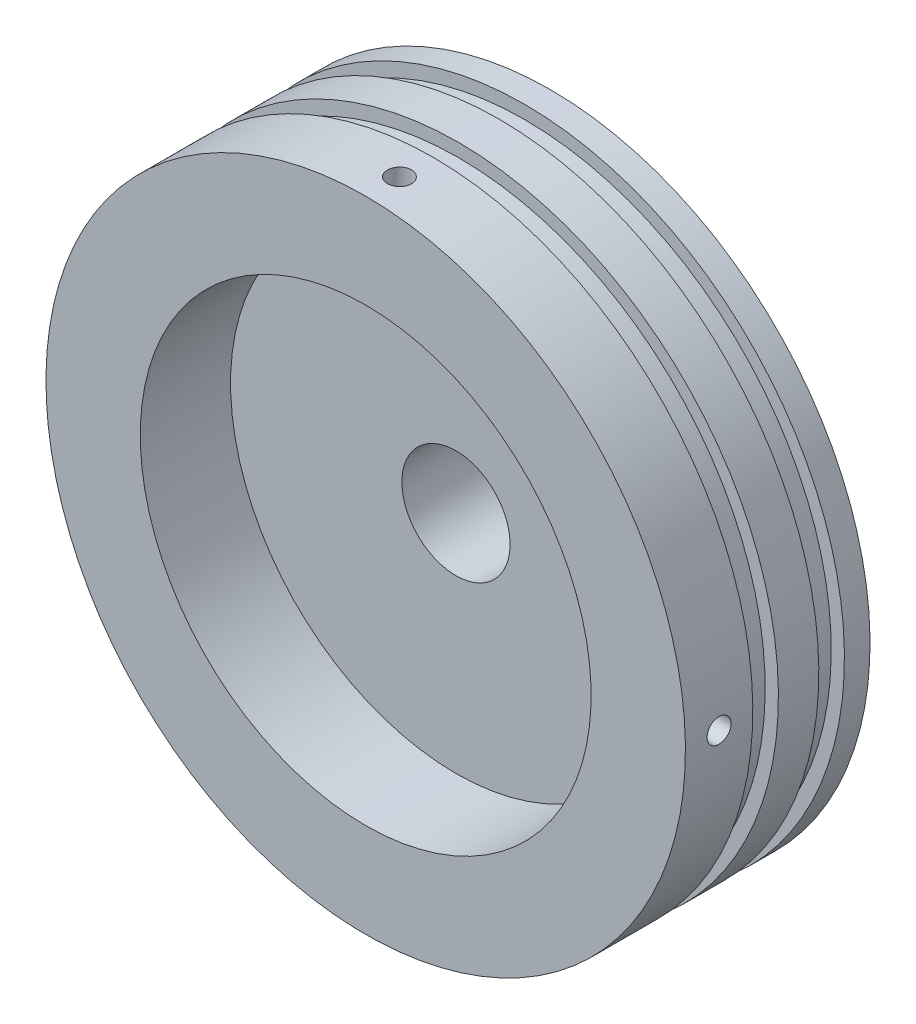
SolidWorks part; units mm, degrees
ref_plane "XY" through (0, 0, 0) normal (0, 0, 1) x (1, 0, 0)
ref_plane "XZ" through (0, 0, 0) normal (0, 1, 0) x (1, 0, 0)
ref_plane "YZ" through (0, 0, 0) normal (1, 0, 0) x (0, 0, -1)
ref_axis "X" through (-33.1508, 0, 0) along (1, 0, 0)
ref_axis "Y" through (0, -33.1508, 0) along (0, 1, 0)
ref_axis "Z" through (0, 0, 18.269) along (0, 0, -1)
sketch "Sketch2" plane through (0, 0, 0) normal (1, 0, 0) x (0, 0, -1)
  line L2 (-17.399, 30.1371) -> (-11.049, 30.1371)
  line L3 (-11.049, 30.1371) -> (-11.049, 28.8925)
  line L4 (-11.049, 28.8925) -> (-8.636, 28.8925)
  line L5 (-8.636, 28.8925) -> (-8.636, 30.1371)
  line L6 (-8.636, 30.1371) -> (-4.826, 30.1371)
  line L7 (-4.826, 30.1371) -> (-4.826, 28.8925)
  line L8 (-4.826, 28.8925) -> (-2.413, 28.8925)
  line L9 (-2.413, 28.8925) -> (-2.413, 30.1371)
  line L10 (-2.413, 30.1371) -> (0, 30.1371)
  line L11 (0, 30.1371) -> (0, 0)
  line L12 (0, 0) -> (-8.89, 0)
  line L13 (-17.399, 30.1371) -> (-17.399, 21.2471)
  line L14 (-17.399, 21.2471) -> (-8.89, 21.2471)
  line L15 (-8.89, 21.2471) -> (-8.89, 0)
  point P0 (-59.4437, 50.5205)
  dimension "D1" = 30.1371
  dimension "D2" = 28.8925
  dimension "D3" = 2.413
  dimension "D4" = 3.81
  dimension "D5" = 2.413
  dimension "D6" = 8.89
  dimension "D7" = 6.35
revolve "Revolve1" add sketch "Sketch2" angle 360 about L12
hole_wizard "#4-40 Tapped Hole1" positions "3DSketch1" profile "Sketch3" tap size "#4-40" standard "ANSI Inch"
sketch3d "3DSketch1"
  line L0 (0, 0, 0) -> (0, 0, 14.224)
  line L1 (0, 0, 14.224) -> (-30.1371, 0, 14.224)
  line L3 (30.1371, 0, 14.224) -> (0, -30.1371, 14.224)
  line L5 (0, -30.1371, 14.224) -> (-30.1371, 0, 14.224)
  line L9 (0, 0, 14.224) -> (0, -30.1371, 14.224)
  line L11 (0, 0, 14.224) -> (30.1371, 0, 14.224)
  line L13 (0, 0, 14.224) -> (0, 30.1371, 14.224)
  line L15 (0, -30.1371, 11.049) -> (0, -30.1371, 17.399)
  line L16 (0, 30.1371, 14.224) -> (-30.1371, 0, 14.224)
  line L18 (30.1371, 0, 14.224) -> (0, 30.1371, 14.224)
  circle A1 centre (0, 0, 11.049) radius 30.1371 construction
  circle A2 centre (0, 0, 17.399) radius 30.1371 construction
  point P5 (0, -30.1371, 14.224)
  point P7 (30.1371, 0, 14.224)
  point P20 (-30.1371, 0, 14.224)
  point P1370 (0, 0, -19.0881)
  point P1373 (0, 0, -12.7381)
  point P1390 (0, 30.1371, 14.224)
  point P1393 (0, 0, 0)
cosmetic thread "Hole Thread2"
cosmetic thread "Hole Thread3"
cosmetic thread "Hole Thread5"
cosmetic thread "Hole Thread6"
sketch "Sketch3" plane through (0, -30.1371, 14.224) normal (1, 0, 0) x (0, 0, -1)
  line L0 (0, 0) -> (0, 8.2992)
  line L1 (0, 8.2992) -> (1.1303, 7.62)
  line L2 (1.1303, 7.62) -> (1.1303, 0)
  line L5 (1.1303, 0) -> (0, 0)
  line L10 (0, 8.2992) -> (-1.1303, 7.62) construction
  line L11 (0, -6.35) -> (0, 107.95) construction
  dimension "Tap Drill Dia." = 2.2606
  dimension "Tap Drill Depth" = 7.62
  dimension "Drill Angle" = 118
hole_wizard "Ø10.2 (10.2) Diameter Hole1" positions "Sketch4" profile "Sketch5" hole size "Ø10.2" standard "ANSI Metric" end condition through all
sketch "Sketch4" plane through (0, 0, 8.89) normal (0, 0, 1) x (1, 0, 0)
  point P0 (0, 0)
sketch "Sketch5" plane through (0, 0, 8.89) normal (1, 0, 0) x (0, -1, 0)
  line L0 (0, 0) -> (0, 8.89)
  line L1 (0, 8.89) -> (5.1, 8.89)
  line L2 (5.1, 8.89) -> (5.1, 0)
  line L5 (5.1, 0) -> (0, 0)
  line L11 (0, -6.35) -> (0, 107.95) construction
  dimension "Thru Hole Dia." = 10.2
  dimension "Thru Hole Depth" = 8.89
